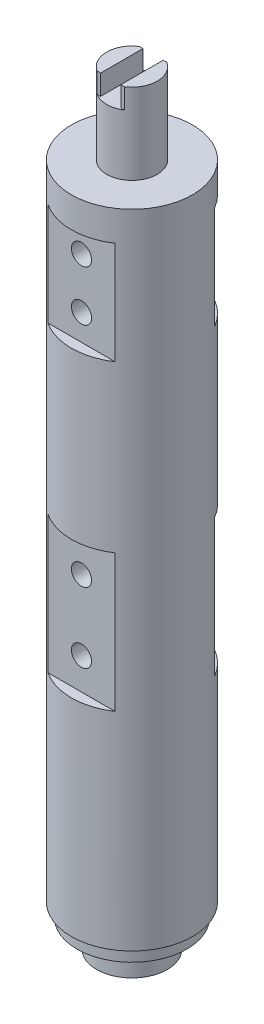
SolidWorks part; units mm, degrees
ref_plane "Front Plane" through (0, 0, 0) normal (0, 0, 1) x (1, 0, 0)
ref_plane "Top Plane" through (0, 0, 0) normal (0, 1, 0) x (1, 0, 0)
ref_plane "Right Plane" through (0, 0, 0) normal (1, 0, 0) x (0, 0, -1)
sketch "Sketch1" plane through (0, 0, 0) normal (0, 1, 0) x (1, 0, 0)
  circle A0 centre (0, 0) radius 19.05
  dimension "D1" = 38.1
extrude "Boss-Extrude1" add sketch "Sketch1" along normal blind 254
sketch "Sketch2" plane through (0, 0, 0) normal (0, 0, 1) x (1, 0, 0)
  line L0 (19.05, 0) -> (11.1125, 0)
  line L1 (11.1125, 0) -> (11.1125, 8.636)
  line L2 (11.1125, 8.636) -> (17.272, 8.636)
  line L3 (17.272, 8.636) -> (17.272, 12.954)
  line L4 (17.272, 12.954) -> (19.05, 12.954)
  line L5 (19.05, 0) -> (19.05, 254) construction
  line L6 (19.05, 254) -> (19.05, 215.011)
  line L7 (19.05, 254) -> (-19.05, 254) construction
  line L8 (19.05, 254) -> (-19.05, 254) construction
  line L9 (19.05, 215.011) -> (7.9375, 215.011)
  line L10 (7.9375, 215.011) -> (7.9375, 254)
  line L11 (7.9375, 254) -> (19.05, 254)
  line L12 (19.05, 0) -> (19.05, 12.954)
  line L13 (0, 348.3373) -> (0, -79.5423) construction
  dimension "D1" = 11.1125
  dimension "D2" = 17.272
  dimension "D3" = 8.636
  dimension "D4" = 4.318
  dimension "D5" = 7.9375
  dimension "D8" = 206.375
revolve "Cut-Revolve1" cut sketch "Sketch2" angle 360 about L13
sketch "Sketch3" plane through (0, 0, 0) normal (1, 0, 0) x (0, 0, -1)
  line L0 (0, 334.7642) -> (0, -20.7307) construction
  line L1 (19.05, 12.954) -> (19.05, 215.011) construction
  line L2 (19.05, 205.486) -> (9.525, 205.486)
  line L3 (19.05, 205.486) -> (19.05, 173.228)
  line L4 (19.05, 173.228) -> (9.525, 173.228)
  line L5 (9.525, 205.486) -> (9.525, 173.228)
  line L6 (19.05, 12.954) -> (19.05, 215.011) construction
  line L7 (19.05, 121.158) -> (9.525, 121.158)
  line L8 (19.05, 121.158) -> (19.05, 77.978)
  line L9 (19.05, 77.978) -> (9.525, 77.978)
  line L10 (9.525, 121.158) -> (9.525, 77.978)
  line L11 (62.8261, 109.982) -> (-27.1107, 109.982) construction
  line L12 (56.0678, 189.357) -> (-35.4285, 189.357) construction
  line L13 (19.05, 215.011) -> (-19.05, 215.011) construction
  line L14 (-19.05, 205.486) -> (-19.05, 173.228)
  line L15 (-19.05, 121.158) -> (-19.05, 77.978)
  line L16 (-19.05, 205.486) -> (-15.875, 205.486)
  line L17 (-15.875, 205.486) -> (-15.875, 173.228)
  line L18 (-15.875, 173.228) -> (-19.05, 173.228)
  line L19 (-19.05, 121.158) -> (-15.875, 121.158)
  line L20 (-15.875, 121.158) -> (-15.875, 77.978)
  line L21 (-15.875, 77.978) -> (-19.05, 77.978)
  dimension "D1" = 43.18
  dimension "D2" = 32.258
  dimension "D3" = 11.176
  dimension "D4" = 79.375
  dimension "D5" = 9.525
  dimension "D6" = 9.525
  dimension "D7" = 3.175
extrude "Cut-Extrude1" cut sketch "Sketch3" against normal through all and the other way through all
hole_wizard "1 (1) Diameter Hole1" positions "Sketch5" profile "Sketch6" hole size "1" standard "ANSI Inch" end condition through all
sketch "Sketch5" plane through (0, 0, -9.525) normal (0, 0, -1) x (-1, 0, 0)
  line L0 (0, 325.237) -> (0, -21.1805) construction
  line L1 (-16.4978, 121.158) -> (16.4978, 121.158) construction
  line L3 (-16.4978, 173.228) -> (-16.4978, 205.486) construction
  line L4 (-16.4978, 173.228) -> (-16.4978, 205.486) construction
  line L5 (-16.4978, 189.357) -> (10.79, 189.357) construction
  point P18 (0, 197.2945)
  point P20 (0, 181.4195)
  point P22 (0, 109.982)
  point P24 (0, 87.884)
  dimension "D1" = 11.176
  dimension "D2" = 22.098
  dimension "D3" = 15.875
sketch "Sketch6" plane through (0, 197.2945, -9.525) normal (1, 0, 0) x (0, 1, 0)
  line L0 (0, 0) -> (0, 28.575)
  line L1 (0, 28.575) -> (3.175, 28.575)
  line L2 (3.175, 28.575) -> (3.175, 0)
  line L5 (3.175, 0) -> (0, 0)
  line L11 (0, -6.35) -> (0, 107.95) construction
  dimension "Thru Hole Dia." = 6.35
  dimension "Thru Hole Depth" = 28.575
sketch "Sketch7" plane through (0, 0, 0) normal (0, 0, 1) x (1, 0, 0)
  line L0 (-7.9375, 254) -> (-7.9375, 215.011) construction
  line L1 (7.9375, 254) -> (-7.9375, 254)
  line L2 (7.9375, 254) -> (7.9375, 240.411)
  line L3 (7.9375, 240.411) -> (-7.9375, 240.411)
  line L4 (-7.9375, 254) -> (-7.9375, 240.411)
  line L5 (7.9375, 215.011) -> (-7.9375, 215.011) construction
  dimension "D1" = 25.4
extrude "Cut-Extrude2" cut sketch "Sketch7" against normal up to next and the other way up to next
sketch "Sketch8" plane through (0, 0, 0) normal (1, 0, 0) x (0, 0, -1)
  line L0 (0, 244.0352) -> (0, 199.4218) construction
  line L1 (7.9375, 240.411) -> (6.6675, 240.411)
  line L2 (7.9375, 240.411) -> (7.9375, 234.061)
  line L3 (7.9375, 234.061) -> (6.6675, 234.061)
  line L4 (6.6675, 240.411) -> (6.6675, 234.061)
  line L5 (-6.6675, 240.411) -> (-6.6675, 234.061)
  line L6 (-7.9375, 234.061) -> (-6.6675, 234.061)
  line L7 (-7.9375, 240.411) -> (-7.9375, 234.061)
  line L8 (-7.9375, 240.411) -> (-6.6675, 240.411)
  dimension "D1" = 6.35
  dimension "D2" = 1.27
extrude "Cut-Extrude3" cut sketch "Sketch8" against normal up to next and the other way up to next
sketch "Sketch9" plane through (0, 240.411, 0) normal (0, 1, 0) x (1, 0, 0)
  line L0 (0, 6.6675) -> (0, -6.6675) construction
  line L1 (4.3068, 6.6675) -> (-4.3068, 6.6675) construction
  line L2 (4.3068, -6.6675) -> (-4.3068, -6.6675) construction
  line L4 (-3.175, -6.6675) -> (3.175, -6.6675)
  line L5 (-3.175, -6.6675) -> (-3.175, 6.6675)
  line L6 (-3.175, 6.6675) -> (3.175, 6.6675)
  line L7 (3.175, -6.6675) -> (3.175, 6.6675)
  line L8 (-3.175, -6.6675) -> (3.175, 6.6675) construction
  line L9 (-3.175, 6.6675) -> (3.175, -6.6675) construction
  point P6 (0, 0)
  dimension "D1" = 6.35
extrude "Cut-Extrude4" cut sketch "Sketch9" against normal blind 6.35
